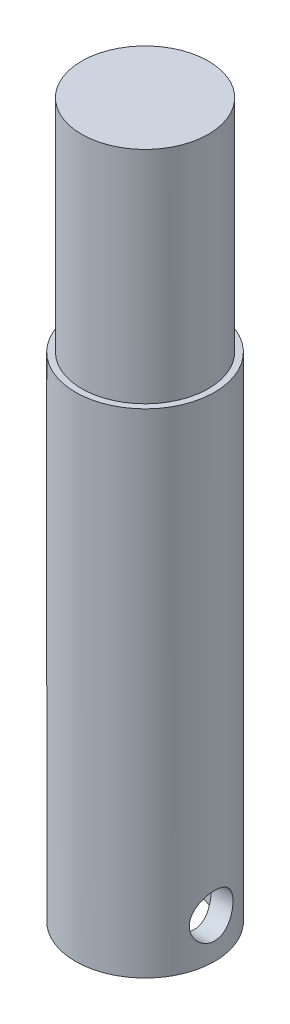
SolidWorks part; units mm, degrees
ref_plane "Front Plane" through (0, 0, 0) normal (0, 0, 1) x (1, 0, 0)
ref_plane "Top Plane" through (0, 0, 0) normal (0, 1, 0) x (1, 0, 0)
ref_plane "Right Plane" through (0, 0, 0) normal (1, 0, 0) x (0, 0, -1)
sketch "Sketch1" plane through (0, 0, 0) normal (0, 1, 0) x (1, 0, 0)
  line L0 (-4.0996, 3) -> (4.0996, 3)
  arc A0 (-4.0996, 3) -> (4.0996, 3) centre (0, 0) ccw
  dimension "D1" = 10.16
  dimension "D2" = 3
extrude "Boss-Extrude1" add sketch "Sketch1" along normal blind 57.15
sketch "Sketch3" plane through (0, 0, 0) normal (0, -1, 0) x (1, 0, 0)
  line L0 (-4.0996, -3) -> (4.0996, -3)
  arc A0 (-4.0996, -3) -> (4.0996, -3) centre (0, 0) ccw
extrude "Boss-Extrude2" add sketch "Sketch3" against normal up to surface (57.15 mm away) up to face at (0, 57.15, 1.04)
sketch "Sketch4" plane through (0, 57.15, 0) normal (0, 1, 0) x (1, 0, 0)
  line L1 (-4.0996, 3) -> (4.0996, 3)
  arc A0 (-4.0996, 3) -> (4.0996, 3) centre (0, 0) cw
extrude "Boss-Extrude3" add sketch "Sketch4" against normal blind 6.35
sketch "Sketch5" plane through (0, 0, 0) normal (0, -1, 0) x (1, 0, 0)
  circle A0 centre (0, 0) radius 3.9688
  dimension "D1" = 7.9375
extrude "Cut-Extrude1" cut sketch "Sketch5" against normal blind 6.35
ref_plane "Plane1" through (5.08, 0, 0) normal (1, 0, 0) x (0, 0, -1)
ref_plane "Plane2" through (0, 6.35, 0) normal (0, -1, 0) x (-1, 0, 0)
sketch "Sketch7" plane through (0, 6.35, 0) normal (0, -1, 0) x (-1, 0, 0)
  circle A0 centre (0, 0) radius 5.5753
  circle A1 centre (0, 0) radius 3.9688
  dimension "D1" = 11.1506
extrude "Boss-Extrude4" add sketch "Sketch7" along normal up to surface (6.35 mm away) and the other way blind 33.147 contours A0 region at (5.4176, 6.35, 0) up to face at (0, 0, -3.9688)
sketch "Sketch6" plane through (5.08, 0, 0) normal (1, 0, 0) x (0, 0, -1)
  circle A0 centre (0, 3.175) radius 1.75
  dimension "D1" = 3.5
  dimension "D2" = 3.175
extrude "Cut-Extrude2" cut sketch "Sketch6" against normal through all both and the other way through all
